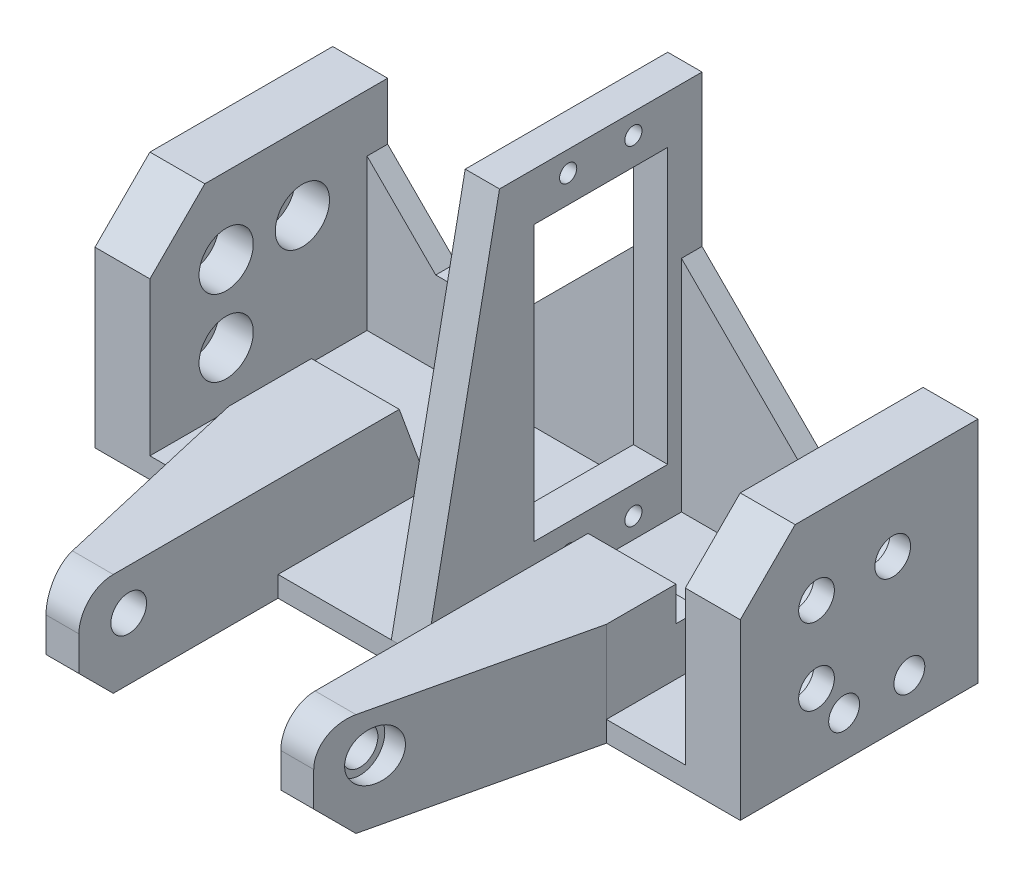
SolidWorks part; units mm, degrees
ref_plane "Спереди" through (0, 0, 0) normal (0, 0, 1) x (1, 0, 0)
ref_plane "Сверху" through (0, 0, 0) normal (0, 1, 0) x (1, 0, 0)
ref_plane "Справа" through (0, 0, 0) normal (1, 0, 0) x (0, 0, -1)
sketch "Эскиз1" plane through (0, 0, 0) normal (0, 0, 1) x (1, 0, 0)
  line L0 (-43.995, 3) -> (43.995, 3)
  line L1 (43.995, 3) -> (43.995, 33.32)
  line L2 (43.995, 33.32) -> (46.995, 33.32)
  line L3 (46.995, 33.32) -> (46.995, 0)
  line L4 (46.995, 0) -> (-46.995, 0)
  line L5 (-46.995, 0) -> (-46.995, 33.32)
  line L6 (-46.995, 33.32) -> (-43.995, 33.32)
  line L7 (-43.995, 33.32) -> (-43.995, 3)
  point P6 (0, 0)
  dimension "D1" = 93.99
  dimension "D2" = 3
  dimension "D3" = 3
  dimension "D4" = 33.32
extrude "Бобышка-Вытянуть1" add sketch "Эскиз1" along normal blind 34.63
sketch "Эскиз2" plane through (-46.995, 0, 0) normal (-1, 0, 0) x (0, 0, 1)
  line L0 (34.63, 33.32) -> (34.63, 0) construction
  line L1 (0, 0) -> (34.63, 0) construction
  line L2 (34.63, 0) -> (0, 0) construction
  line L3 (34.63, 0) -> (34.63, 33.32) construction
  line L4 (34.63, 33.32) -> (0, 33.32) construction
  line L5 (34.63, 33.32) -> (1.31, 33.32) construction
  line L6 (1.31, 33.32) -> (12.4186, 22.2114) construction
  line L7 (34.63, 0) -> (23.5214, 11.1086) construction
  line L8 (34.63, 33.32) -> (23.5214, 22.2114) construction
  line L9 (1.31, 33.32) -> (1.31, 0) construction
  line L10 (1.31, 0) -> (34.63, 0) construction
  circle A0 centre (12.4186, 22.2114) radius 2.6
  circle A1 centre (23.5214, 22.2114) radius 2.6
  circle A2 centre (23.5214, 11.1086) radius 2.6
  dimension "D2" = 5.2
  dimension "D1" = 15.71
extrude "Вырез-Вытянуть1" cut sketch "Эскиз2" against normal through all
sketch "Эскиз3" plane through (0, 0, 0) normal (0, 1, 0) x (1, 0, 0)
  line L0 (-27.5, -34.63) -> (27.5, -34.63)
  line L1 (43.995, -34.63) -> (-43.995, -34.63) construction
  line L2 (27.5, -34.63) -> (19.5, -69.26)
  line L3 (19.5, -69.26) -> (-19.5, -69.26) construction
  line L4 (-19.5, -69.26) -> (-27.5, -34.63)
  line L5 (0, -69.26) -> (0, -34.63) construction
  line L6 (0, -34.63) -> (0, 0) construction
  line L7 (-19.5, -69.26) -> (-14.7, -69.26)
  line L8 (-14.7, -69.26) -> (-14.7, -40.26)
  line L9 (-14.7, -40.26) -> (14.7, -40.26)
  line L10 (14.7, -40.26) -> (14.7, -69.26)
  line L11 (14.7, -69.26) -> (19.5, -69.26)
  dimension "D1" = 34.63
  dimension "D2" = 39
  dimension "D3" = 4.8
  dimension "D4" = 29
  dimension "D5" = 55
extrude "Бобышка-Вытянуть2" add sketch "Эскиз3" along normal blind 3
sketch "Эскиз4" plane through (14.7, 0, 0) normal (-1, 0, 0) x (0, 0, 1)
  line L0 (69.26, 3) -> (22.6004, 3)
  line L1 (22.6004, 3) -> (22.6004, 15)
  line L2 (22.6004, 15) -> (69.26, 15)
  line L3 (69.26, 15) -> (69.26, 3)
  line L4 (69.26, 9) -> (54.76, 9) construction
  circle A0 centre (62.01, 9) radius 2.6
  dimension "D3" = 5.2
  dimension "D1" = 12
  dimension "D2" = 14.5
extrude "Бобышка-Вытянуть3" add sketch "Эскиз4" against normal up to vertex (12.8 mm away) up to point (27.5, 0, 34.63)
draft "Уклон1" type of draft neutral plane draft angle 20 faces to draft 1 face at (21.1, 9, 22.6004) neutral plane through (27.5, 15, 22.6004) neutral plane normal (0, 1, 0) parameters "D1"=20
sketch "Эскиз5" plane through (0, 3, 0) normal (0, -1, 0) x (1, 0, 0)
  line L0 (27.5, 34.63) -> (27.5, 69.26) construction
  line L1 (27.5, 69.26) -> (19.5, 69.26) construction
  line L2 (19.5, 69.26) -> (27.5, 34.63) construction
  line L3 (27.5, 34.63) -> (27.5, 69.26)
  line L4 (27.5, 69.26) -> (19.5, 69.26)
  line L5 (19.5, 69.26) -> (27.5, 34.63)
extrude "Вырез-Вытянуть2" cut sketch "Эскиз5" against normal through all
sketch "Эскиз6" plane through (46.995, 0, 0) normal (1, 0, 0) x (0, 0, -1)
  circle A0 centre (-62.01, 9) radius 3.6
  dimension "D1" = 7.2
extrude "Вырез-Вытянуть3" cut sketch "Эскиз6" against normal blind 28
fillet "Скругление1" radius 5 1 edges at (17.1, 15, 69.26)
chamfer "Фаска1" distance 5 angle 45 1 edges at (17.1, 0, 69.26)
mirror "Зеркальное отражение3" about plane through (0, 0, 0) normal (1, 0, 0) of "Вырез-Вытянуть3", "Вырез-Вытянуть2", "Уклон1", "Бобышка-Вытянуть3"
chamfer "Фаска2" distance 5 angle 45 1 edges at (-17.1, 0, 69.26)
fillet "Скругление2" radius 5 1 edges at (-17.1, 15, 69.26)
sketch "Эскиз7" plane through (0, 3, 0) normal (0, 1, 0) x (1, 0, 0)
  line L0 (43.995, -34.63) -> (43.995, 0) construction
  line L1 (-43.995, 0) -> (43.995, 0)
  line L2 (-43.995, 0) -> (-43.995, -3)
  line L3 (-43.995, -3) -> (43.995, -3)
  line L4 (43.995, 0) -> (43.995, -3)
  dimension "D1" = 3
extrude "Бобышка-Вытянуть4" add sketch "Эскиз7" along normal blind 12
sketch "Эскиз8" plane through (43.995, 0, 0) normal (-1, 0, 0) x (0, 0, 1)
  line L0 (3, 3) -> (34.63, 3)
  line L1 (34.63, 3) -> (34.63, 33.32)
  line L2 (34.63, 33.32) -> (0, 33.32)
  line L3 (0, 33.32) -> (0, 15)
  line L4 (0, 15) -> (3, 15)
  line L5 (3, 15) -> (3, 3)
  circle A0 centre (12.4186, 22.2114) radius 3.95
  circle A1 centre (23.5214, 22.2114) radius 3.95
  circle A2 centre (23.5214, 11.1086) radius 3.95
  dimension "D1" = 7.9
extrude "Бобышка-Вытянуть5" add sketch "Эскиз8" along normal blind 5
mirror "Зеркальное отражение4" about plane through (0, 0, 0) normal (1, 0, 0) of "Бобышка-Вытянуть5"
chamfer "Фаска3" distance 8 angle 45 2 edges at (-42.995, 33.32, 34.63) (42.995, 33.32, 34.63)
chamfer "Фаска4" distance 10 angle 45 2 edges at (38.995, 15, 1.5) (-38.995, 15, 1.5)
ref_plane "Плоскость1" through (6.8, 0, 0) normal (1, 0, 0) x (0, 0, -1)
sketch "Эскиз9" plane through (6.8, 0, 0) normal (1, 0, 0) x (0, 0, -1)
  line L0 (-29.5, 10) -> (-29.5, 50)
  line L1 (-24.5, 10) -> (-5, 10)
  line L2 (-24.5, 10) -> (-24.5, 50)
  line L3 (-24.5, 50) -> (-5, 50)
  line L4 (-5, 10) -> (-5, 50)
  line L5 (-24.5, 57) -> (-5, 57)
  line L6 (-24.5, 3) -> (-5, 3)
  line L7 (0, 10) -> (0, 50)
  line L8 (0, 50) -> (0, 57)
  line L9 (0, 57) -> (-5, 57)
  line L10 (-29.5, 50) -> (-29.5, 57)
  line L11 (-29.5, 57) -> (-24.5, 57)
  line L12 (-29.5, 10) -> (-29.5, 3)
  line L13 (-29.5, 3) -> (-24.5, 3)
  line L14 (-5, 3) -> (0, 3)
  line L15 (0, 3) -> (0, 10)
  line L16 (-34.63, 0) -> (0, 0) construction
  line L17 (0, 0) -> (0, 33.32) construction
  dimension "D1" = 40
  dimension "D2" = 19.5
  dimension "D7" = 3
  dimension "D3" = 5
  dimension "D4" = 7
  dimension "D5" = 7
  dimension "D6" = 5
extrude "Бобышка-Вытянуть6" add sketch "Эскиз9" against normal blind 5 contours L14 L15 L7 L8 L9 L5 L11 L10 L0 L12 L13 L6 L4 L1 L2 L3 region at (6.8, 30, 28.8847)
extrude "Вырез-Вытянуть4" cut sketch "Эскиз9<3>" along normal blind 30 contours L1 L4 L3 L2 region at (6.8, 30, 14.75)
sketch "Эскиз9<3>" plane through (6.8, 0, 0) normal (1, 0, 0) x (0, 0, -1) same geometry as "Эскиз9"
sketch "Эскиз10" plane through (6.8, 0, 0) normal (1, 0, 0) x (0, 0, -1)
  line L0 (-29.5, 3) -> (-29.5, 57)
  line L1 (-29.5, 57) -> (-40.26, 3)
  line L2 (-40.26, 3) -> (-29.5, 3)
  point P5 (0, 0)
extrude "Бобышка-Вытянуть7" add sketch "Эскиз10" against normal blind 5
chamfer "Фаска5" distance 20 angle 45 2 edges at (1.8, 15, 1.5) (6.8, 15, 1.5)
sketch "Эскиз11" plane through (6.8, 0, 0) normal (1, 0, 0) x (0, 0, -1)
  line L0 (-14.75, 50) -> (-14.75, 54) construction
  line L1 (-24.5, 50) -> (-5, 50) construction
  line L2 (-19.5, 54) -> (-10, 54) construction
  circle A0 centre (-19.5, 54) radius 1.25
  circle A1 centre (-10, 54) radius 1.25
  point P8 (0, 0)
  point P9 (-14.75, 54)
  dimension "D1" = 2.5
  dimension "D2" = 9.5
  dimension "D3" = 4
extrude "Вырез-Вытянуть5" cut sketch "Эскиз11" against normal blind 5
ref_plane "Плоскость2" through (0, 30, 0) normal (0, 1, 0) x (1, 0, 0)
mirror "Зеркальное отражение5" about plane through (0, 30, 0) normal (0, 1, 0) of "Вырез-Вытянуть5"
sketch "Эскиз12" plane through (6.8, 0, 0) normal (1, 0, 0) x (0, 0, -1)
  circle A5 centre (-19.5, 6) radius 2.25
  circle A6 centre (-19.5, 6) radius 2.25
  circle A8 centre (-10, 6) radius 2.25
  circle A9 centre (-10, 6) radius 2.25
  dimension "D1" = 1
  dimension "D2" = 1
extrude "Вырез-Вытянуть6" cut sketch "Эскиз12" along normal through all
